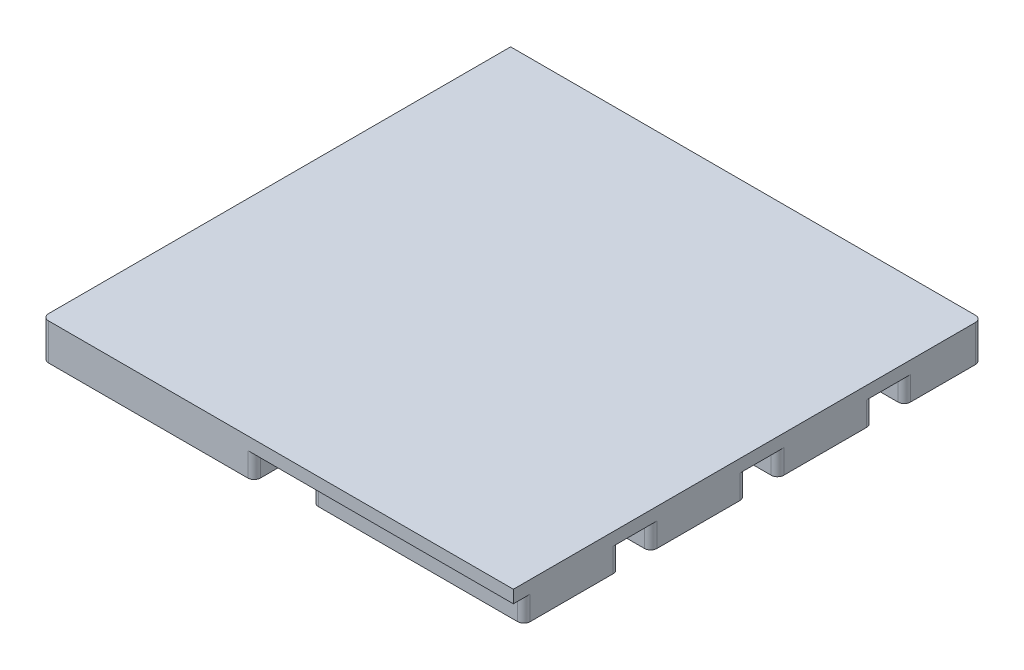
SolidWorks part; units mm, degrees
ref_plane "Front Plane" through (0, 0, 0) normal (0, 0, 1) x (1, 0, 0)
ref_plane "Top Plane" through (0, 0, 0) normal (0, 1, 0) x (1, 0, 0)
ref_plane "Right Plane" through (0, 0, 0) normal (1, 0, 0) x (0, 0, -1)
sketch "Sketch2" plane through (0, 0, 0) normal (0, 1, 0) x (1, 0, 0)
  line L1 (0, 0) -> (149, 0)
  line L2 (0, 0) -> (0, 148.13)
  line L3 (0, 148.13) -> (149, 148.13)
  line L4 (149, 0) -> (149, 148.13)
  dimension "D1" = 149
  dimension "D2" = 148.13
extrude "Boss-Extrude1" add sketch "Sketch2" along normal blind 4
sketch "Sketch3" plane through (0, 4, 0) normal (0, 1, 0) x (1, 0, 0)
  line L0 (0, 148.13) -> (0, 0) construction
  line L1 (149, 148.13) -> (82, 148.13)
  line L2 (149, 148.13) -> (149, 123.63)
  line L3 (149, 123.63) -> (82, 123.63)
  line L4 (82, 148.13) -> (82, 123.63)
  line L5 (0, 144.7967) -> (67, 144.7967)
  line L6 (0, 144.7967) -> (0, 120.2967)
  line L7 (0, 120.2967) -> (67, 120.2967)
  line L8 (67, 144.7967) -> (67, 120.2967)
  line L9 (149, 148.13) -> (0, 148.13) construction
  line L10 (149, 0) -> (149, 148.13) construction
  line L11 (149, 113.73) -> (82, 113.73)
  line L12 (149, 113.73) -> (149, 83.53)
  line L13 (149, 83.53) -> (82, 83.53)
  line L14 (82, 113.73) -> (82, 83.53)
  line L15 (97.3, 113.73) -> (97.3, 99.43) construction
  line L16 (0, 110.3967) -> (67, 110.3967)
  line L17 (0, 110.3967) -> (0, 80.1967)
  line L18 (0, 80.1967) -> (67, 80.1967)
  line L19 (67, 110.3967) -> (67, 80.1967)
  line L20 (149, 73.63) -> (82, 73.63)
  line L21 (149, 73.63) -> (149, 43.43)
  line L22 (149, 43.43) -> (82, 43.43)
  line L23 (82, 73.63) -> (82, 43.43)
  line L24 (0, 70.2967) -> (67, 70.2967)
  line L25 (0, 70.2967) -> (0, 40.0967)
  line L26 (0, 40.0967) -> (67, 40.0967)
  line L27 (67, 70.2967) -> (67, 40.0967)
  line L28 (0, 30.1967) -> (67, 30.1967)
  line L29 (0, 30.1967) -> (0, -0.0033)
  line L30 (0, -0.0033) -> (67, -0.0033)
  line L31 (67, 30.1967) -> (67, -0.0033)
  line L32 (97.3, 99.43) -> (97.3, 95.83) construction
  line L33 (149, 33.53) -> (82, 33.53)
  line L34 (149, 33.53) -> (149, 3.33)
  line L35 (149, 3.33) -> (82, 3.33)
  line L36 (82, 33.53) -> (82, 3.33)
  line L37 (12.85, 144.7967) -> (12.85, 137.4467) construction
  line L38 (12.85, 137.4467) -> (40.15, 137.4467)
  line L39 (12.85, 137.4467) -> (12.85, 133.7967) construction
  line L40 (12.85, 133.7967) -> (12.85, 120.2967) construction
  line L41 (12.85, 133.7967) -> (40.15, 133.7967)
  line L42 (97.3, 148.13) -> (97.3, 140.13) construction
  line L43 (97.3, 140.13) -> (97.3, 136.48) construction
  line L44 (97.3, 136.48) -> (97.3, 123.63) construction
  line L45 (97.3, 140.13) -> (124.6, 140.13)
  line L46 (97.3, 136.48) -> (124.6, 136.48)
  line L47 (0, 0) -> (149, 0) construction
  line L48 (97.3, 95.83) -> (97.3, 83.53) construction
  line L49 (97.3, 99.43) -> (124.6, 99.43)
  line L50 (97.3, 95.83) -> (124.6, 95.83)
  line L51 (12.85, 110.3967) -> (12.85, 96.0967) construction
  line L52 (12.85, 96.0967) -> (12.85, 92.4967) construction
  line L53 (12.85, 92.4967) -> (12.85, 80.1967) construction
  line L54 (12.85, 96.0967) -> (40.15, 96.0967)
  line L55 (12.85, 92.4967) -> (40.15, 92.4967)
  line L56 (12.85, 70.2967) -> (12.85, 55.9967) construction
  line L57 (12.85, 55.9967) -> (12.85, 52.3967) construction
  line L58 (12.85, 52.3967) -> (12.85, 40.0967) construction
  line L59 (12.85, 55.9967) -> (40.15, 55.9967)
  line L60 (12.85, 52.3967) -> (40.15, 52.3967)
  line L61 (97.3, 73.63) -> (97.3, 59.33) construction
  line L62 (97.3, 59.33) -> (97.3, 55.73) construction
  line L63 (97.3, 55.73) -> (97.3, 43.43) construction
  line L64 (97.3, 59.33) -> (124.6, 59.33)
  line L65 (97.3, 55.73) -> (124.6, 55.73)
  line L66 (12.85, 30.1967) -> (12.85, 15.8967) construction
  line L67 (12.85, 15.8967) -> (12.85, 12.2967) construction
  line L68 (12.85, 12.2967) -> (12.85, -0.0033) construction
  line L69 (12.85, 15.8967) -> (40.15, 15.8967)
  line L70 (12.85, 12.2967) -> (40.15, 12.2967)
  line L71 (97.3, 33.53) -> (97.3, 19.23) construction
  line L72 (97.3, 19.23) -> (97.3, 15.63) construction
  line L73 (97.3, 15.63) -> (97.3, 3.33) construction
  line L74 (97.3, 19.23) -> (124.6, 19.23)
  line L75 (97.3, 15.63) -> (124.6, 15.63)
  arc A0 (12.85, 133.7967) -> (12.85, 137.4467) centre (12.85, 135.6217) cw
  arc A2 (40.15, 137.4467) -> (40.15, 133.7967) centre (40.15, 135.6217) cw
  arc A3 (97.3, 136.48) -> (97.3, 140.13) centre (97.3, 138.305) cw
  arc A4 (124.6, 140.13) -> (124.6, 136.48) centre (124.6, 138.305) cw
  arc A5 (97.3, 95.83) -> (97.3, 99.43) centre (97.3, 97.63) cw
  arc A6 (124.6, 99.43) -> (124.6, 95.83) centre (124.6, 97.63) cw
  arc A7 (12.85, 92.4967) -> (12.85, 96.0967) centre (12.85, 94.2967) cw
  arc A9 (40.15, 92.4967) -> (40.15, 96.0967) centre (40.15, 94.2967) ccw
  arc A10 (12.85, 52.3967) -> (12.85, 55.9967) centre (12.85, 54.1967) cw
  arc A11 (40.15, 55.9967) -> (40.15, 52.3967) centre (40.15, 54.1967) cw
  arc A12 (97.3, 55.73) -> (97.3, 59.33) centre (97.3, 57.53) cw
  arc A13 (124.6, 59.33) -> (124.6, 55.73) centre (124.6, 57.53) cw
  arc A14 (12.85, 12.2967) -> (12.85, 15.8967) centre (12.85, 14.0967) cw
  arc A15 (40.15, 15.8967) -> (40.15, 12.2967) centre (40.15, 14.0967) cw
  arc A16 (97.3, 15.63) -> (97.3, 19.23) centre (97.3, 17.43) cw
  arc A17 (124.6, 19.23) -> (124.6, 15.63) centre (124.6, 17.43) cw
  line M24 (0, 148.13) -> (0, 0)
  line M25 (0, 0) -> (149, 0)
  line M26 (149, 0) -> (149, 148.13)
  line M27 (149, 148.13) -> (0, 148.13)
  dimension "D31" = 24.4
  dimension "D1" = 67
  dimension "D2" = 24.5
  dimension "D3" = 3.3333
  dimension "D4" = 67
  dimension "D5" = 24.5
  dimension "D6" = 9.9
  dimension "D7" = 30.2
  dimension "D8" = 67
  dimension "D9" = 30.2
  dimension "D10" = 9.9
  dimension "D11" = 67
  dimension "D12" = 9.9
  dimension "D13" = 30.2
  dimension "D14" = 67
  dimension "D15" = 9.9
  dimension "D16" = 30.2
  dimension "D17" = 67
  dimension "D18" = 30.2
  dimension "D19" = 9.9
  dimension "D20" = 67
  dimension "D21" = 9.9
  dimension "D22" = 30.2
  dimension "D23" = 67
  dimension "D24" = 7.35
  dimension "D25" = 3.65
  dimension "D26" = 27.3
  dimension "D27" = 12.85
  dimension "D28" = 8
  dimension "D29" = 3.65
  dimension "D30" = 27.3
  dimension "D32" = 14.3
  dimension "D33" = 12.3
  dimension "D34" = 27.3
  dimension "D35" = 14.3
  dimension "D36" = 12.3
  dimension "D37" = 27.3
  dimension "D38" = 14.3
  dimension "D39" = 12.3
  dimension "D40" = 14.3
  dimension "D41" = 12.3
  dimension "D42" = 14.3
  dimension "D43" = 12.3
  dimension "D44" = 14.3
  dimension "D45" = 12.3
extrude "Boss-Extrude3" add sketch "Sketch3" against normal blind 11.55 contours L8 L5 L7 L38 A2 L41 A0 M24 | L4 L3 L45 A4 L46 A3 M27 M26 | L19 L16 L18 A9 L55 A7 L54 M24 | L11 L14 L13 L49 A6 L50 A5 M26 | L27 L24 L26 L59 A11 L60 A10 M24 | L20 L23 L22 L64 A13 L65 A12 M26 | L31 L28 L69 A15 L70 A14 M24 M25 | L33 L36 L35 L74 A17 L75 A16 M26 region at (115.8271, 4, -135.7056) region at (148.2651, 4, -98.63) region at (34.0033, 4, -132.3256) region at (148.2651, 4, -58.53) region at (33.5, 4, -109.6618) region at (148.2651, 4, -18.43) region at (33.5, 4, -69.5618) region at (33.5, 4, -29.4618)
fillet "Fillet1" radius 2 32 edges at (149, -3.775, -3.33) (149, -3.775, -33.53) (82, -3.775, -33.53) (82, -3.775, -3.33) (67, -3.775, 0) (0, -1.775, 0) (0, -3.775, -30.1967) (67, -3.775, -30.1967) (67, -3.775, -40.0967) (0, -3.775, -40.0967) (149, -3.775, -43.43) (82, -3.775, -43.43) (82, -3.775, -73.63) (67, -3.775, -70.2967) (0, -3.775, -70.2967) (0, -3.775, -80.1967) (82, -3.775, -83.53) (67, -3.775, -80.1967) (0, -3.775, -110.3967) (149, -3.775, -83.53) (149, -3.775, -73.63) (149, -3.775, -113.73) (67, -3.775, -110.3967) (82, -3.775, -113.73) (0, -3.775, -120.2967) (67, -3.775, -120.2967) (67, -3.775, -144.7967) (0, -3.775, -144.7967) (82, -3.775, -123.63) (149, -3.775, -123.63) (149, -1.775, -148.13) (82, -3.775, -148.13)
